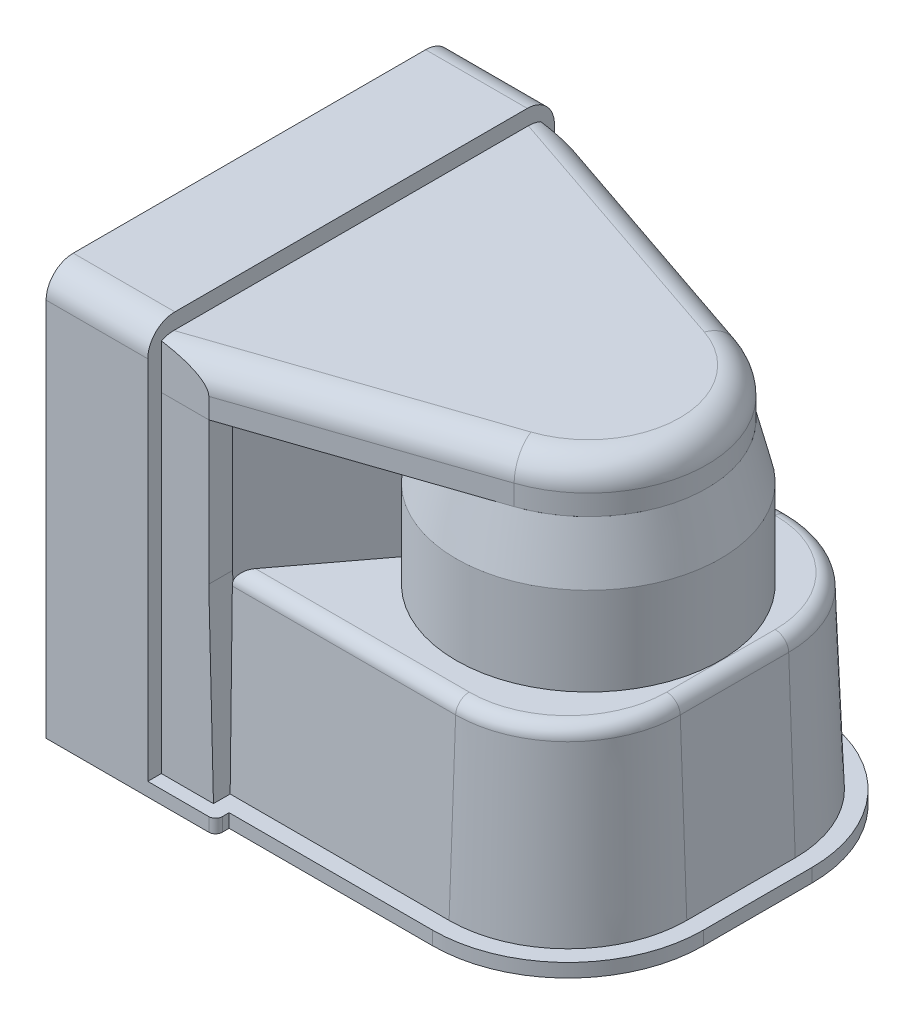
SolidWorks part; units mm, degrees
ref_plane "Plan de face" through (0, 0, 0) normal (0, 0, 1) x (1, 0, 0)
ref_plane "Plan de dessus" through (0, 0, 0) normal (0, 1, 0) x (1, 0, 0)
ref_plane "Plan de droite" through (0, 0, 0) normal (1, 0, 0) x (0, 0, -1)
sketch "Esquisse1" plane through (0, 0, 0) normal (1, 0, 0) x (0, 0, -1)
  line L1 (0, 0) -> (60, 0)
  line L2 (0, 0) -> (0, 60)
  line L3 (0, 60) -> (60, 60)
  line L4 (60, 0) -> (60, 60)
  circle A0 centre (7, 23) radius 2
  circle A1 centre (53, 23) radius 2
  dimension "D3" = 4
  dimension "D4" = 46
  dimension "D1" = 60
  dimension "D2" = 60
  dimension "D5" = 7
  dimension "D6" = 23
  dimension "D7" = 23
extrude "Boss.-Extru.1" add sketch "Esquisse1" along normal blind 15
sketch "Esquisse2" plane through (0, 0, 0) normal (0, -1, 0) x (1, 0, 0)
  line L0 (0, -30) -> (89.6097, -30) construction
  line L1 (0, 0) -> (0, -60) construction
  line L2 (75, -9.4891) -> (75, -51.8361) construction
  line L3 (15, 0) -> (24, 0)
  line L4 (15, 0) -> (15, -60) construction
  line L5 (25, -1) -> (25, -2)
  line L6 (25, -2) -> (55, -2)
  line L7 (75, -22) -> (75, -38)
  line L8 (55, -58) -> (25, -58)
  line L9 (25, -58) -> (25, -59)
  line L10 (24, -60) -> (15, -60)
  line L11 (15, -60) -> (15, 0)
  line L12 (15, -60) -> (0, -60) construction
  line L13 (15, 0) -> (0, 0) construction
  arc A0 (75, -22) -> (55, -2) centre (55, -22) ccw
  arc A1 (55, -58) -> (75, -38) centre (55, -38) ccw
  arc A2 (24, -60) -> (25, -59) centre (24, -59) ccw
  arc A3 (25, -1) -> (24, 0) centre (24, -1) ccw
  point P4 (50, -30)
  point P25 (75, -58)
  dimension "D5" = 20
  dimension "D6" = 20
  dimension "D7" = 1
  dimension "D1" = 50
  dimension "D2" = 25
  dimension "D3" = 2
  dimension "D4" = 2
  dimension "D8" = 10
extrude "Boss.-Extru.2" add sketch "Esquisse2" against normal blind 2
sketch "Esquisse3" plane through (0, 2, 0) normal (0, 1, 0) x (1, 0, 0)
  line L11 (23, 2) -> (15, 2)
  line L12 (15, 0) -> (15, 60) construction
  line L13 (15, 2) -> (15, 58)
  line L14 (15, 58) -> (23, 58)
  line L19 (17, 58) -> (17, 2)
  line L20 (17, 2) -> (23, 2)
  line L21 (23, 2) -> (23, 4)
  line L22 (23, 4) -> (55, 4)
  line L23 (73, 22) -> (73, 38)
  line L24 (55, 56) -> (23, 56)
  line L25 (23, 2) -> (23, 4)
  line L26 (23, 58) -> (17, 58)
  line L27 (17, 58) -> (17, 2) construction
  line L28 (17, 2) -> (23, 2) construction
  line L29 (23, 56) -> (23, 58)
  line L30 (23, 4) -> (55, 4)
  line L31 (73, 22) -> (73, 38)
  line L32 (55, 56) -> (23, 56)
  line L33 (23, 56) -> (23, 58)
  line L34 (23, 58) -> (17, 58) construction
  arc A11 (55, 4) -> (73, 22) centre (55, 22) ccw
  arc A12 (73, 38) -> (55, 56) centre (55, 38) ccw
  arc A15 (55, 4) -> (73, 22) centre (55, 22) ccw
  arc A16 (73, 38) -> (55, 56) centre (55, 38) ccw
  dimension "D1" = 2
extrude "Boss.-Extru.3" add sketch "Esquisse3" along normal blind 27.7
chamfer "Chanfrein1" distance 40 distance2 1.5 5 edges at (39, 29.7, -56) (67.7279, 29.7, -50.7279) (39, 29.7, -4) (73, 29.7, -30) (67.7279, 29.7, -9.2721) first distance on face at (39, 15.85, -56) first distance on face at (65.864, 15.85, -48.864) first distance on face at (39, 15.85, -4) first distance on face at (73, 15.85, -30) first distance on face at (65.864, 15.85, -11.136)
chamfer "Chanfrein2" distance 40 distance2 1 2 edges at (23, 29.7, -56.25) (23, 29.7, -3.75) first distance on face at (23, 15.85, -56.5097) first distance on face at (23, 15.85, -3.4903)
sketch "Esquisse4" plane through (0, 29.7, 0) normal (0, 1, 0) x (1, 0, 0)
  line L0 (0, 30) -> (78.1546, 30) construction
  line L1 (0, 60) -> (0, 0) construction
  line L2 (50, 30) -> (1.8954, 57.7732) construction
  line L3 (50, 30) -> (-2.3515, -0.2251) construction
  line L4 (22, 54.5) -> (33.1125, 39.75)
  line L5 (33.1125, 20.25) -> (22, 5.5)
  line L6 (22, 54.5) -> (22, 58)
  line L7 (22, 58) -> (15, 58)
  line L8 (15, 58) -> (15, 2)
  line L9 (15, 2) -> (22, 2)
  line L10 (22, 2) -> (22, 5.5)
  circle A0 centre (50, 30) radius 19.5 construction
  arc A2 (33.1125, 20.25) -> (33.1125, 39.75) centre (50, 30) cw
  point P4 (50, 30)
  dimension "D2" = 39
  dimension "D1" = 50
  dimension "D3" = 30
  dimension "D4" = 30
extrude "Boss.-Extru.4" add sketch "Esquisse4" along normal blind 21
sketch "Esquisse5" plane through (0, 29.7, 0) normal (0, 1, 0) x (1, 0, 0)
  circle A0 centre (50, 30) radius 19.5
extrude "Boss.-Extru.5" add sketch "Esquisse5" along normal blind 13 separate body
sketch "Esquisse6" plane through (0, 42.7, 0) normal (0, 1, 0) x (1, 0, 0)
  circle A0 centre (50, 30) radius 19.5
extrude "Boss.-Extru.6" add sketch "Esquisse6" along normal blind 8 separate body
chamfer "Chanfrein3" distance 8 distance2 2 1 edges at (50, 50.7, -10.5) first distance on face at (50, 50.7, -10.5)
sketch "Esquisse8" plane through (0, 50.7, 0) normal (0, 1, 0) x (1, 0, 0)
  line L0 (15, 2) -> (22, 2)
  line L1 (22, 2) -> (55.6316, 13.4309)
  line L2 (15, 2) -> (15, 58)
  line L3 (15, 58) -> (22, 58)
  line L4 (22, 58) -> (55.6316, 46.5691)
  circle A0 centre (50, 30) radius 17.5 construction
  arc A1 (55.6316, 46.5691) -> (55.6316, 13.4309) centre (50, 30) cw
extrude "Boss.-Extru.9" add sketch "Esquisse8" along normal blind 7 separate body
fillet "Congé3" radius 2 5 edges at (38.5, 29.7, -5.5) (38.5, 29.7, -54.5) (66.6673, 29.7, -49.6673) (71.5, 29.7, -30) (66.6673, 29.7, -10.3327)
fillet "Congé4" radius 4 3 edges at (38.8158, 57.7, -7.7154) (38.8158, 57.7, -52.2846) (67.5, 57.7, -30)
fillet "Congé5" radius 4 2 edges at (7.5, 60, -60) (7.5, 60, 0)
